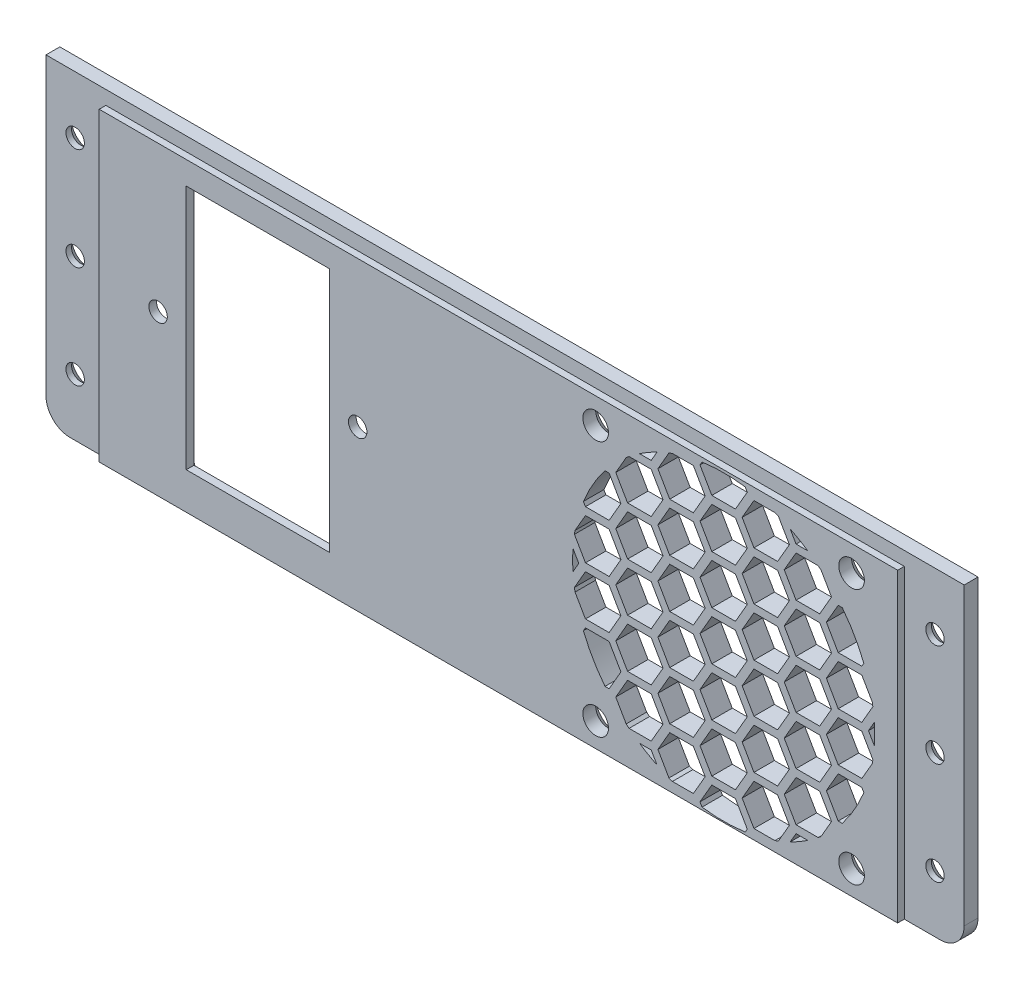
SolidWorks part; units mm, degrees
ref_plane "Front Plane" through (0, 0, 0) normal (0, 0, 1) x (1, 0, 0)
ref_plane "Top Plane" through (0, 0, 0) normal (0, 1, 0) x (1, 0, 0)
ref_plane "Right Plane" through (0, 0, 0) normal (1, 0, 0) x (0, 0, -1)
sketch "Sketch1" plane through (0, 0, 0) normal (0, 0, 1) x (1, 0, 0)
  line L1 (-90, -31.5) -> (90, -31.5)
  line L2 (-90, -31.5) -> (-90, 31.5)
  line L3 (-90, 31.5) -> (90, 31.5)
  line L4 (90, -31.5) -> (90, 31.5)
  line L5 (-90, -31.5) -> (90, 31.5) construction
  line L6 (-90, 31.5) -> (90, -31.5) construction
  point P0 (0, 0)
  dimension "D1" = 180
  dimension "D2" = 63
extrude "Boss-Extrude1" add sketch "Sketch1" along normal blind 3
fillet "Fillet1" radius 5 2 edges at (-90, -31.5, 1.5) (90, -31.5, 1.5)
sketch "Sketch2" plane through (0, 0, 3) normal (0, 0, 1) x (1, 0, 0)
  line L0 (-85, -31.5) -> (85, -31.5) construction
  line L1 (-78, -31.5) -> (78, -31.5)
  line L2 (-78, -31.5) -> (-78, 31.5)
  line L3 (-78, 31.5) -> (78, 31.5)
  line L4 (78, -31.5) -> (78, 31.5)
  line L5 (90, 31.5) -> (-90, 31.5) construction
  dimension "D1" = 12
  dimension "D2" = 12
extrude "Boss-Extrude2" add sketch "Sketch2" along normal blind 4
sketch "Sketch3" plane through (0, 0, 0) normal (0, 0, -1) x (-1, 0, 0)
  line L0 (-90, -26.5) -> (-90, 31.5) construction
  line L2 (90, -26.5) -> (90, 31.5) construction
  point P0 (-84, 20)
  point P2 (-84, -20)
  point P4 (84, 20)
  point P6 (84, -20)
  point P8 (-84, 0)
  point P10 (84, 0)
  dimension "D1" = 6
  dimension "D2" = 20
  dimension "D3" = 20
  dimension "D4" = 6
  dimension "D5" = 20
  dimension "D6" = 20
hole_wizard "CSK for M3 Flat Head Machine Screw1" positions "Sketch3" profile "Sketch4" countersink size "M3" standard "ANSI Metric"
sketch "Sketch4" plane through (84, 20, 0) normal (1, 0, 0) x (0, 1, 0)
  line L0 (0, 0) -> (0, 9.0815)
  line L1 (0, 9.0815) -> (1.8, 8)
  line L2 (1.8, 8) -> (1.8, 1.6)
  line L3 (1.8, 1.6) -> (3.4, 0)
  line L5 (3.4, 0) -> (0, 0)
  line L6 (-1.8, 1.6) -> (-3.4, 0) construction
  line L10 (0, 9.0815) -> (-1.8, 8) construction
  line L11 (0, -6.35) -> (0, 107.95) construction
  dimension "Hole Dia." = 3.6
  dimension "Hole Depth" = 8
  dimension "Near C'Sink Dia." = 6.8
  dimension "Near C'Sink Angle" = 90
  dimension "Drill Angle" = 118
sketch "Sketch5" plane through (0, 0, 0) normal (0, 0, -1) x (-1, 0, 0)
  line L0 (32, 30) -> (21, 0)
  line L1 (62, 30) -> (32, 30)
  line L2 (62, 30) -> (62, -30)
  line L3 (62, -30) -> (32, -30)
  line L4 (32, 30) -> (32, -30)
  line L5 (21, 0) -> (32, -30)
  line L6 (62, -30) -> (73, 0)
  line L7 (73, 0) -> (62, 30)
  line L8 (90, 31.5) -> (90, -26.5) construction
  point P8 (62, 0)
  dimension "D1" = 30
  dimension "D2" = 60
  dimension "D3" = 11
  dimension "D4" = 11
  dimension "D5" = 28
extrude "Cut-Extrude1" cut sketch "Sketch5" against normal blind 2.5 contours L0 L5 L4 | L1 L4 L3 L2 | L6 L7 L2 region at (-28.3333, 0, 0) region at (-47, 0, 0) region at (-65.6667, 0, 0)
sketch "Sketch6" plane through (0, 0, 2.5) normal (0, 0, -1) x (-1, 0, 0)
  line L0 (62, 30) -> (32, 30) construction
  line L1 (61, -24) -> (33, -24)
  line L2 (61, -24) -> (61, 24)
  line L3 (61, 24) -> (33, 24)
  line L4 (33, -24) -> (33, 24)
  line L5 (61, -24) -> (33, 24) construction
  line L6 (61, 24) -> (33, -24) construction
  point P0 (47, 0)
  point P7 (47, 30)
  dimension "D1" = 28
  dimension "D2" = 48
extrude "Cut-Extrude2" cut sketch "Sketch6" against normal through all
fillet "Fillet2" radius 2 6 edges at (-21, 0, 1.25) (-32, -30, 1.25) (-62, -30, 1.25) (-73, 0, 1.25) (-62, 30, 1.25) (-32, 30, 1.25)
sketch "Sketch7" plane through (0, 0, 2.5) normal (0, 0, -1) x (-1, 0, 0)
  line L0 (27.5, 0) -> (66.5, 0) construction
  line L2 (61, 24) -> (33, 24) construction
  point P0 (27.5, 0)
  point P2 (66.5, 0)
  point P15 (47, 24)
  point P16 (47, 0)
  dimension "D1" = 39
hole_wizard "M3 Clearance Hole1" positions "Sketch7" profile "Sketch8" hole size "M3" standard "ANSI Metric"
sketch "Sketch8" plane through (-27.5, 0, 2.5) normal (1, 0, 0) x (0, 1, 0)
  line L0 (0, 0) -> (0, 9.0815)
  line L1 (0, 9.0815) -> (1.8, 8)
  line L2 (1.8, 8) -> (1.8, 0)
  line L5 (1.8, 0) -> (0, 0)
  line L10 (0, 9.0815) -> (-1.8, 8) construction
  line L11 (0, -6.35) -> (0, 107.95) construction
  dimension "Hole Dia." = 3.6
  dimension "Hole Depth" = 8
  dimension "Drill Angle" = 118
sketch "Sketch9" plane through (0, 0, 7) normal (0, 0, 1) x (1, 0, 0)
  line L0 (-78, -31.5) -> (78, -31.5) construction
  line L1 (14, -31.5) -> (74, -31.5)
  line L2 (14, -31.5) -> (14, 28.5)
  line L3 (14, 28.5) -> (74, 28.5)
  line L4 (74, -31.5) -> (74, 28.5)
  line L5 (14, -31.5) -> (74, 28.5) construction
  line L6 (14, 28.5) -> (74, -31.5) construction
  line L11 (78, -31.5) -> (78, 31.5) construction
  line L13 (69, -26.5) -> (19, -26.5)
  line L14 (69, -26.5) -> (69, 23.5)
  line L15 (69, 23.5) -> (19, 23.5)
  line L16 (19, -26.5) -> (19, 23.5)
  line L17 (69, -26.5) -> (19, 23.5) construction
  line L18 (69, 23.5) -> (19, -26.5) construction
  point P0 (44, -1.5)
  point P10 (44, -1.5)
  dimension "D1" = 60
  dimension "D2" = 60
  dimension "D3" = 4
  dimension "D4" = 50
sketch "Sketch12" plane through (0, 0, 0) normal (0, 0, -1) x (-1, 0, 0)
  point P0 (-19, 23.5)
  point P2 (-19, -26.5)
  point P4 (-69, -26.5)
  point P6 (-69, 23.5)
hole_wizard "CSK for M4 Flat Head Machine Screw2" positions "Sketch12" profile "Sketch14" countersink size "M4" standard "ANSI Metric" end condition through all
sketch "Sketch14" plane through (19, 23.5, 0) normal (1, 0, 0) x (0, 1, 0)
  line L0 (0, 0) -> (0, 7)
  line L1 (0, 7) -> (2.5, 7)
  line L2 (2.5, 7) -> (2.5, 1.5)
  line L3 (2.5, 1.5) -> (4, 0)
  line L5 (4, 0) -> (0, 0)
  line L6 (-2.5, 1.5) -> (-4, 0) construction
  line L11 (0, -6.35) -> (0, 107.95) construction
  dimension "Thru Hole Dia." = 5
  dimension "Thru Hole Depth" = 7
  dimension "Near C'Sink Dia." = 8
  dimension "Near C'Sink Angle" = 90
sketch "Sketch15" plane through (0, 0, 7) normal (0, 0, 1) x (1, 0, 0)
  line L0 (-78, -31.5) -> (78, -31.5) construction
  line L1 (74, -31.5) -> (-21, -31.5)
  line L2 (74, -31.5) -> (74, 31.5)
  line L3 (74, 31.5) -> (-21, 31.5)
  line L4 (-21, -31.5) -> (-21, 31.5)
  line L5 (78, 31.5) -> (-78, 31.5) construction
  line L6 (78, -31.5) -> (78, 31.5) construction
  dimension "D1" = 4
  dimension "D2" = 95
extrude "Cut-Extrude3" cut sketch "Sketch15" against normal blind 3
sketch "Sketch16" plane through (0, 0, 0) normal (0, 0, -1) x (-1, 0, 0)
  circle A4 centre (-64, 13.5) radius 4
  circle A53 centre (-69, 23.5) radius 4 construction
  circle A54 centre (-69, 23.5) radius 4
  circle A55 centre (-19, 23.5) radius 4 construction
  circle A56 centre (-19, 23.5) radius 4
  circle A57 centre (-59, 23.5) radius 4
  circle A58 centre (-49, 23.5) radius 4
  circle A59 centre (-39, 23.5) radius 4
  circle A60 centre (-29, 23.5) radius 4
  circle A61 centre (-54, 13.5) radius 4
  circle A62 centre (-44, 13.5) radius 4
  circle A63 centre (-34, 13.5) radius 4
  circle A64 centre (-24, 13.5) radius 4
  circle A65 centre (-14, 13.5) radius 4
  circle A66 centre (-4, 13.5) radius 4
  circle A67 centre (6, 13.5) radius 4
  circle A68 centre (-54, -6.5) radius 4
  circle A69 centre (-44, -6.5) radius 4
  circle A70 centre (-34, -6.5) radius 4
  circle A71 centre (-24, -6.5) radius 4
  circle A72 centre (-14, -6.5) radius 4
  circle A73 centre (-4, -6.5) radius 4
  circle A74 centre (6, -6.5) radius 4
  circle A75 centre (-64, -6.5) radius 4
  circle A76 centre (-59, 23.5) radius 4
  circle A77 centre (-49, 23.5) radius 4
  circle A78 centre (-39, 23.5) radius 4
  circle A79 centre (-29, 23.5) radius 4
  circle A80 centre (-19, 23.5) radius 4
  circle A81 centre (-9, 23.5) radius 4
  circle A82 centre (1, 23.5) radius 4
  circle A83 centre (-59, 3.5) radius 4
  circle A84 centre (-49, 3.5) radius 4
  circle A85 centre (-39, 3.5) radius 4
  circle A86 centre (-29, 3.5) radius 4
  circle A87 centre (-19, 3.5) radius 4
  circle A88 centre (-9, 3.5) radius 4
  circle A89 centre (1, 3.5) radius 4
  circle A90 centre (-59, -16.5) radius 4
  circle A91 centre (-49, -16.5) radius 4
  circle A92 centre (-39, -16.5) radius 4
  circle A93 centre (-29, -16.5) radius 4
  circle A94 centre (-19, -16.5) radius 4
  circle A95 centre (-9, -16.5) radius 4
  circle A96 centre (1, -16.5) radius 4
  circle A97 centre (-69, 3.5) radius 4
  circle A98 centre (-69, -16.5) radius 4
  dimension "D1" = 5
  dimension "D2" = 10
  dimension "D3" = 5
sketch "Sketch17" plane through (0, 0, 0) normal (0, 0, -1) x (-1, 0, 0)
  circle A0 centre (-44, -1.5) radius 29.5
  dimension "D1" = 59
extrude "Cut-Extrude7" cut sketch "Sketch17" against normal through all
sketch "Sketch18" plane through (0, 31.5, 0) normal (0, 1, 0) x (1, 0, 0)
  line L1 (-90, -3) -> (90, -3)
  line L2 (-90, -3) -> (-90, -11)
  line L3 (-90, -11) -> (90, -11)
  line L4 (90, -3) -> (90, -11)
  dimension "D1" = 8
extrude "Cut-Extrude8" cut sketch "Sketch18" against normal blind 3
sketch "Sketch20" plane through (0, 0, 0) normal (0, 0, -1) x (-1, 0, 0)
  line L0 (-90, -26.5) -> (-90, 31.5) construction
  line L1 (-10, 28) -> (20, 28)
  line L2 (-10, 28) -> (-10, -31)
  line L3 (-10, -31) -> (20, -31)
  line L4 (20, 28) -> (20, -31)
  line L5 (-10, 28) -> (20, -31) construction
  line L6 (-10, -31) -> (20, 28) construction
  circle A0 centre (-44, -1.5) radius 29.5 construction
  point P0 (5, -1.5)
  dimension "D1" = 30
  dimension "D2" = 95
extrude "Cut-Extrude9" cut sketch "Sketch20" against normal through all
sketch "Sketch19" plane through (0, 0, 0) normal (0, 0, -1) x (-1, 0, 0)
  line L0 (-44, -1.5) -> (-35.7728, 3.25) construction
  line L1 (-39.3812, -1.5) -> (-41.6906, 2.5)
  line L2 (-41.6906, 2.5) -> (-46.3094, 2.5)
  line L3 (-46.3094, 2.5) -> (-48.6188, -1.5)
  line L4 (-48.6188, -1.5) -> (-46.3094, -5.5)
  line L5 (-46.3094, -5.5) -> (-41.6906, -5.5)
  line L6 (-41.6906, -5.5) -> (-39.3812, -1.5)
  line L7 (-31.154, 3.25) -> (-33.4634, 7.25)
  line L8 (-33.4634, 7.25) -> (-38.0822, 7.25)
  line L9 (-38.0822, 7.25) -> (-40.3916, 3.25)
  line L10 (-40.3916, 3.25) -> (-38.0822, -0.75)
  line L11 (-38.0822, -0.75) -> (-33.4634, -0.75)
  line L12 (-33.4634, -0.75) -> (-31.154, 3.25)
  line L13 (-44, -1.5) -> (-35.7728, -1.5) construction
  line L14 (-39.3812, -11) -> (-41.6906, -7)
  line L15 (-41.6906, -7) -> (-46.3094, -7)
  line L16 (-46.3094, -7) -> (-48.6188, -11)
  line L17 (-48.6188, -11) -> (-46.3094, -15)
  line L18 (-46.3094, -15) -> (-41.6906, -15)
  line L19 (-41.6906, -15) -> (-39.3812, -11)
  line L20 (-31.154, -6.25) -> (-33.4634, -2.25)
  line L21 (-33.4634, -2.25) -> (-38.0822, -2.25)
  line L22 (-38.0822, -2.25) -> (-40.3916, -6.25)
  line L23 (-40.3916, -6.25) -> (-38.0822, -10.25)
  line L24 (-38.0822, -10.25) -> (-33.4634, -10.25)
  line L25 (-33.4634, -10.25) -> (-31.154, -6.25)
  line L26 (-22.9212, -1.5) -> (-25.2306, 2.5)
  line L27 (-25.2306, 2.5) -> (-29.8494, 2.5)
  line L28 (-29.8494, 2.5) -> (-32.1588, -1.5)
  line L29 (-32.1588, -1.5) -> (-29.8494, -5.5)
  line L30 (-29.8494, -5.5) -> (-25.2306, -5.5)
  line L31 (-25.2306, -5.5) -> (-22.9212, -1.5)
  line L32 (-6.4612, -1.5) -> (-8.7706, 2.5)
  line L33 (-8.7706, 2.5) -> (-13.3894, 2.5)
  line L34 (-13.3894, 2.5) -> (-15.6988, -1.5)
  line L35 (-15.6988, -1.5) -> (-13.3894, -5.5)
  line L36 (-13.3894, -5.5) -> (-8.7706, -5.5)
  line L37 (-8.7706, -5.5) -> (-6.4612, -1.5)
  line L38 (-22.9212, -11) -> (-25.2306, -7)
  line L39 (-25.2306, -7) -> (-29.8494, -7)
  line L40 (-29.8494, -7) -> (-32.1588, -11)
  line L41 (-32.1588, -11) -> (-29.8494, -15)
  line L42 (-29.8494, -15) -> (-25.2306, -15)
  line L43 (-25.2306, -15) -> (-22.9212, -11)
  line L44 (-6.4612, -11) -> (-8.7706, -7)
  line L45 (-8.7706, -7) -> (-13.3894, -7)
  line L46 (-13.3894, -7) -> (-15.6988, -11)
  line L47 (-15.6988, -11) -> (-13.3894, -15)
  line L48 (-13.3894, -15) -> (-8.7706, -15)
  line L49 (-8.7706, -15) -> (-6.4612, -11)
  line L50 (-22.9212, -20.5) -> (-25.2306, -16.5)
  line L51 (-25.2306, -16.5) -> (-29.8494, -16.5)
  line L52 (-29.8494, -16.5) -> (-32.1588, -20.5)
  line L53 (-32.1588, -20.5) -> (-29.8494, -24.5)
  line L54 (-29.8494, -24.5) -> (-25.2306, -24.5)
  line L55 (-25.2306, -24.5) -> (-22.9212, -20.5)
  line L56 (-6.4612, -20.5) -> (-8.7706, -16.5)
  line L57 (-8.7706, -16.5) -> (-13.3894, -16.5)
  line L58 (-13.3894, -16.5) -> (-15.6988, -20.5)
  line L59 (-15.6988, -20.5) -> (-13.3894, -24.5)
  line L60 (-13.3894, -24.5) -> (-8.7706, -24.5)
  line L61 (-8.7706, -24.5) -> (-6.4612, -20.5)
  line L62 (-22.9212, -30) -> (-25.2306, -26)
  line L63 (-25.2306, -26) -> (-29.8494, -26)
  line L64 (-29.8494, -26) -> (-32.1588, -30)
  line L65 (-32.1588, -30) -> (-29.8494, -34)
  line L66 (-29.8494, -34) -> (-25.2306, -34)
  line L67 (-25.2306, -34) -> (-22.9212, -30)
  line L68 (-6.4612, -30) -> (-8.7706, -26)
  line L69 (-8.7706, -26) -> (-13.3894, -26)
  line L70 (-13.3894, -26) -> (-15.6988, -30)
  line L71 (-15.6988, -30) -> (-13.3894, -34)
  line L72 (-13.3894, -34) -> (-8.7706, -34)
  line L73 (-8.7706, -34) -> (-6.4612, -30)
  line L74 (-39.3812, -11) -> (-41.6906, -7)
  line L75 (-41.6906, -7) -> (-46.3094, -7)
  line L76 (-46.3094, -7) -> (-48.6188, -11)
  line L77 (-48.6188, -11) -> (-46.3094, -15)
  line L78 (-46.3094, -15) -> (-41.6906, -15)
  line L79 (-41.6906, -15) -> (-39.3812, -11)
  line L80 (-39.3812, -20.5) -> (-41.6906, -16.5)
  line L81 (-41.6906, -16.5) -> (-46.3094, -16.5)
  line L82 (-46.3094, -16.5) -> (-48.6188, -20.5)
  line L83 (-48.6188, -20.5) -> (-46.3094, -24.5)
  line L84 (-46.3094, -24.5) -> (-41.6906, -24.5)
  line L85 (-41.6906, -24.5) -> (-39.3812, -20.5)
  line L86 (-39.3812, -30) -> (-41.6906, -26)
  line L87 (-41.6906, -26) -> (-46.3094, -26)
  line L88 (-46.3094, -26) -> (-48.6188, -30)
  line L89 (-48.6188, -30) -> (-46.3094, -34)
  line L90 (-46.3094, -34) -> (-41.6906, -34)
  line L91 (-41.6906, -34) -> (-39.3812, -30)
  line L92 (-39.3812, 8) -> (-41.6906, 12)
  line L93 (-41.6906, 12) -> (-46.3094, 12)
  line L94 (-46.3094, 12) -> (-48.6188, 8)
  line L95 (-48.6188, 8) -> (-46.3094, 4)
  line L96 (-46.3094, 4) -> (-41.6906, 4)
  line L97 (-41.6906, 4) -> (-39.3812, 8)
  line L98 (-22.9212, 8) -> (-25.2306, 12)
  line L99 (-25.2306, 12) -> (-29.8494, 12)
  line L100 (-29.8494, 12) -> (-32.1588, 8)
  line L101 (-32.1588, 8) -> (-29.8494, 4)
  line L102 (-29.8494, 4) -> (-25.2306, 4)
  line L103 (-25.2306, 4) -> (-22.9212, 8)
  line L104 (-6.4612, 8) -> (-8.7706, 12)
  line L105 (-8.7706, 12) -> (-13.3894, 12)
  line L106 (-13.3894, 12) -> (-15.6988, 8)
  line L107 (-15.6988, 8) -> (-13.3894, 4)
  line L108 (-13.3894, 4) -> (-8.7706, 4)
  line L109 (-8.7706, 4) -> (-6.4612, 8)
  line L110 (-39.3812, 17.5) -> (-41.6906, 21.5)
  line L111 (-41.6906, 21.5) -> (-46.3094, 21.5)
  line L112 (-46.3094, 21.5) -> (-48.6188, 17.5)
  line L113 (-48.6188, 17.5) -> (-46.3094, 13.5)
  line L114 (-46.3094, 13.5) -> (-41.6906, 13.5)
  line L115 (-41.6906, 13.5) -> (-39.3812, 17.5)
  line L116 (-22.9212, 17.5) -> (-25.2306, 21.5)
  line L117 (-25.2306, 21.5) -> (-29.8494, 21.5)
  line L118 (-29.8494, 21.5) -> (-32.1588, 17.5)
  line L119 (-32.1588, 17.5) -> (-29.8494, 13.5)
  line L120 (-29.8494, 13.5) -> (-25.2306, 13.5)
  line L121 (-25.2306, 13.5) -> (-22.9212, 17.5)
  line L122 (-6.4612, 17.5) -> (-8.7706, 21.5)
  line L123 (-8.7706, 21.5) -> (-13.3894, 21.5)
  line L124 (-13.3894, 21.5) -> (-15.6988, 17.5)
  line L125 (-15.6988, 17.5) -> (-13.3894, 13.5)
  line L126 (-13.3894, 13.5) -> (-8.7706, 13.5)
  line L127 (-8.7706, 13.5) -> (-6.4612, 17.5)
  line L128 (-39.3812, 27) -> (-41.6906, 31)
  line L129 (-41.6906, 31) -> (-46.3094, 31)
  line L130 (-46.3094, 31) -> (-48.6188, 27)
  line L131 (-48.6188, 27) -> (-46.3094, 23)
  line L132 (-46.3094, 23) -> (-41.6906, 23)
  line L133 (-41.6906, 23) -> (-39.3812, 27)
  line L134 (-22.9212, 27) -> (-25.2306, 31)
  line L135 (-25.2306, 31) -> (-29.8494, 31)
  line L136 (-29.8494, 31) -> (-32.1588, 27)
  line L137 (-32.1588, 27) -> (-29.8494, 23)
  line L138 (-29.8494, 23) -> (-25.2306, 23)
  line L139 (-25.2306, 23) -> (-22.9212, 27)
  line L140 (-6.4612, 27) -> (-8.7706, 31)
  line L141 (-8.7706, 31) -> (-13.3894, 31)
  line L142 (-13.3894, 31) -> (-15.6988, 27)
  line L143 (-15.6988, 27) -> (-13.3894, 23)
  line L144 (-13.3894, 23) -> (-8.7706, 23)
  line L145 (-8.7706, 23) -> (-6.4612, 27)
  line L146 (-31.154, 12.75) -> (-33.4634, 16.75)
  line L147 (-33.4634, 16.75) -> (-38.0822, 16.75)
  line L148 (-38.0822, 16.75) -> (-40.3916, 12.75)
  line L149 (-40.3916, 12.75) -> (-38.0822, 8.75)
  line L150 (-38.0822, 8.75) -> (-33.4634, 8.75)
  line L151 (-33.4634, 8.75) -> (-31.154, 12.75)
  line L152 (-31.154, 22.25) -> (-33.4634, 26.25)
  line L153 (-33.4634, 26.25) -> (-38.0822, 26.25)
  line L154 (-38.0822, 26.25) -> (-40.3916, 22.25)
  line L155 (-40.3916, 22.25) -> (-38.0822, 18.25)
  line L156 (-38.0822, 18.25) -> (-33.4634, 18.25)
  line L157 (-33.4634, 18.25) -> (-31.154, 22.25)
  line L158 (-31.154, -15.75) -> (-33.4634, -11.75)
  line L159 (-33.4634, -11.75) -> (-38.0822, -11.75)
  line L160 (-38.0822, -11.75) -> (-40.3916, -15.75)
  line L161 (-40.3916, -15.75) -> (-38.0822, -19.75)
  line L162 (-38.0822, -19.75) -> (-33.4634, -19.75)
  line L163 (-33.4634, -19.75) -> (-31.154, -15.75)
  line L164 (-31.154, -25.25) -> (-33.4634, -21.25)
  line L165 (-33.4634, -21.25) -> (-38.0822, -21.25)
  line L166 (-38.0822, -21.25) -> (-40.3916, -25.25)
  line L167 (-40.3916, -25.25) -> (-38.0822, -29.25)
  line L168 (-38.0822, -29.25) -> (-33.4634, -29.25)
  line L169 (-33.4634, -29.25) -> (-31.154, -25.25)
  line L170 (-31.154, -34.75) -> (-33.4634, -30.75)
  line L171 (-33.4634, -30.75) -> (-38.0822, -30.75)
  line L172 (-38.0822, -30.75) -> (-40.3916, -34.75)
  line L173 (-40.3916, -34.75) -> (-38.0822, -38.75)
  line L174 (-38.0822, -38.75) -> (-33.4634, -38.75)
  line L175 (-33.4634, -38.75) -> (-31.154, -34.75)
  line L176 (-14.694, 22.25) -> (-17.0034, 26.25)
  line L177 (-17.0034, 26.25) -> (-21.6222, 26.25)
  line L178 (-21.6222, 26.25) -> (-23.9316, 22.25)
  line L179 (-23.9316, 22.25) -> (-21.6222, 18.25)
  line L180 (-21.6222, 18.25) -> (-17.0034, 18.25)
  line L181 (-17.0034, 18.25) -> (-14.694, 22.25)
  line L182 (-14.694, 12.75) -> (-17.0034, 16.75)
  line L183 (-17.0034, 16.75) -> (-21.6222, 16.75)
  line L184 (-21.6222, 16.75) -> (-23.9316, 12.75)
  line L185 (-23.9316, 12.75) -> (-21.6222, 8.75)
  line L186 (-21.6222, 8.75) -> (-17.0034, 8.75)
  line L187 (-17.0034, 8.75) -> (-14.694, 12.75)
  line L188 (-14.694, 3.25) -> (-17.0034, 7.25)
  line L189 (-17.0034, 7.25) -> (-21.6222, 7.25)
  line L190 (-21.6222, 7.25) -> (-23.9316, 3.25)
  line L191 (-23.9316, 3.25) -> (-21.6222, -0.75)
  line L192 (-21.6222, -0.75) -> (-17.0034, -0.75)
  line L193 (-17.0034, -0.75) -> (-14.694, 3.25)
  line L194 (-14.694, -6.25) -> (-17.0034, -2.25)
  line L195 (-17.0034, -2.25) -> (-21.6222, -2.25)
  line L196 (-21.6222, -2.25) -> (-23.9316, -6.25)
  line L197 (-23.9316, -6.25) -> (-21.6222, -10.25)
  line L198 (-21.6222, -10.25) -> (-17.0034, -10.25)
  line L199 (-17.0034, -10.25) -> (-14.694, -6.25)
  line L200 (-14.694, -15.75) -> (-17.0034, -11.75)
  line L201 (-17.0034, -11.75) -> (-21.6222, -11.75)
  line L202 (-21.6222, -11.75) -> (-23.9316, -15.75)
  line L203 (-23.9316, -15.75) -> (-21.6222, -19.75)
  line L204 (-21.6222, -19.75) -> (-17.0034, -19.75)
  line L205 (-17.0034, -19.75) -> (-14.694, -15.75)
  line L206 (-14.694, -25.25) -> (-17.0034, -21.25)
  line L207 (-17.0034, -21.25) -> (-21.6222, -21.25)
  line L208 (-21.6222, -21.25) -> (-23.9316, -25.25)
  line L209 (-23.9316, -25.25) -> (-21.6222, -29.25)
  line L210 (-21.6222, -29.25) -> (-17.0034, -29.25)
  line L211 (-17.0034, -29.25) -> (-14.694, -25.25)
  line L212 (-55.8412, 27) -> (-58.1506, 31)
  line L213 (-58.1506, 31) -> (-62.7694, 31)
  line L214 (-62.7694, 31) -> (-65.0788, 27)
  line L215 (-65.0788, 27) -> (-62.7694, 23)
  line L216 (-62.7694, 23) -> (-58.1506, 23)
  line L217 (-58.1506, 23) -> (-55.8412, 27)
  line L218 (-55.8412, 17.5) -> (-58.1506, 21.5)
  line L219 (-58.1506, 21.5) -> (-62.7694, 21.5)
  line L220 (-62.7694, 21.5) -> (-65.0788, 17.5)
  line L221 (-65.0788, 17.5) -> (-62.7694, 13.5)
  line L222 (-62.7694, 13.5) -> (-58.1506, 13.5)
  line L223 (-58.1506, 13.5) -> (-55.8412, 17.5)
  line L224 (-47.614, 22.25) -> (-49.9234, 26.25)
  line L225 (-49.9234, 26.25) -> (-54.5422, 26.25)
  line L226 (-54.5422, 26.25) -> (-56.8516, 22.25)
  line L227 (-56.8516, 22.25) -> (-54.5422, 18.25)
  line L228 (-54.5422, 18.25) -> (-49.9234, 18.25)
  line L229 (-49.9234, 18.25) -> (-47.614, 22.25)
  line L230 (-47.614, 12.75) -> (-49.9234, 16.75)
  line L231 (-49.9234, 16.75) -> (-54.5422, 16.75)
  line L232 (-54.5422, 16.75) -> (-56.8516, 12.75)
  line L233 (-56.8516, 12.75) -> (-54.5422, 8.75)
  line L234 (-54.5422, 8.75) -> (-49.9234, 8.75)
  line L235 (-49.9234, 8.75) -> (-47.614, 12.75)
  line L236 (-55.8412, 8) -> (-58.1506, 12)
  line L237 (-58.1506, 12) -> (-62.7694, 12)
  line L238 (-62.7694, 12) -> (-65.0788, 8)
  line L239 (-65.0788, 8) -> (-62.7694, 4)
  line L240 (-62.7694, 4) -> (-58.1506, 4)
  line L241 (-58.1506, 4) -> (-55.8412, 8)
  line L242 (-47.614, 3.25) -> (-49.9234, 7.25)
  line L243 (-49.9234, 7.25) -> (-54.5422, 7.25)
  line L244 (-54.5422, 7.25) -> (-56.8516, 3.25)
  line L245 (-56.8516, 3.25) -> (-54.5422, -0.75)
  line L246 (-54.5422, -0.75) -> (-49.9234, -0.75)
  line L247 (-49.9234, -0.75) -> (-47.614, 3.25)
  line L248 (-55.8412, -1.5) -> (-58.1506, 2.5)
  line L249 (-58.1506, 2.5) -> (-62.7694, 2.5)
  line L250 (-62.7694, 2.5) -> (-65.0788, -1.5)
  line L251 (-65.0788, -1.5) -> (-62.7694, -5.5)
  line L252 (-62.7694, -5.5) -> (-58.1506, -5.5)
  line L253 (-58.1506, -5.5) -> (-55.8412, -1.5)
  line L254 (-47.614, -6.25) -> (-49.9234, -2.25)
  line L255 (-49.9234, -2.25) -> (-54.5422, -2.25)
  line L256 (-54.5422, -2.25) -> (-56.8516, -6.25)
  line L257 (-56.8516, -6.25) -> (-54.5422, -10.25)
  line L258 (-54.5422, -10.25) -> (-49.9234, -10.25)
  line L259 (-49.9234, -10.25) -> (-47.614, -6.25)
  line L260 (-55.8412, -11) -> (-58.1506, -7)
  line L261 (-58.1506, -7) -> (-62.7694, -7)
  line L262 (-62.7694, -7) -> (-65.0788, -11)
  line L263 (-65.0788, -11) -> (-62.7694, -15)
  line L264 (-62.7694, -15) -> (-58.1506, -15)
  line L265 (-58.1506, -15) -> (-55.8412, -11)
  line L266 (-47.614, -15.75) -> (-49.9234, -11.75)
  line L267 (-49.9234, -11.75) -> (-54.5422, -11.75)
  line L268 (-54.5422, -11.75) -> (-56.8516, -15.75)
  line L269 (-56.8516, -15.75) -> (-54.5422, -19.75)
  line L270 (-54.5422, -19.75) -> (-49.9234, -19.75)
  line L271 (-49.9234, -19.75) -> (-47.614, -15.75)
  line L272 (-55.8412, -20.5) -> (-58.1506, -16.5)
  line L273 (-58.1506, -16.5) -> (-62.7694, -16.5)
  line L274 (-62.7694, -16.5) -> (-65.0788, -20.5)
  line L275 (-65.0788, -20.5) -> (-62.7694, -24.5)
  line L276 (-62.7694, -24.5) -> (-58.1506, -24.5)
  line L277 (-58.1506, -24.5) -> (-55.8412, -20.5)
  line L278 (-47.614, -25.25) -> (-49.9234, -21.25)
  line L279 (-49.9234, -21.25) -> (-54.5422, -21.25)
  line L280 (-54.5422, -21.25) -> (-56.8516, -25.25)
  line L281 (-56.8516, -25.25) -> (-54.5422, -29.25)
  line L282 (-54.5422, -29.25) -> (-49.9234, -29.25)
  line L283 (-49.9234, -29.25) -> (-47.614, -25.25)
  line L284 (-55.8412, -30) -> (-58.1506, -26)
  line L285 (-58.1506, -26) -> (-62.7694, -26)
  line L286 (-62.7694, -26) -> (-65.0788, -30)
  line L287 (-65.0788, -30) -> (-62.7694, -34)
  line L288 (-62.7694, -34) -> (-58.1506, -34)
  line L289 (-58.1506, -34) -> (-55.8412, -30)
  line L290 (-47.614, -34.75) -> (-49.9234, -30.75)
  line L291 (-49.9234, -30.75) -> (-54.5422, -30.75)
  line L292 (-54.5422, -30.75) -> (-56.8516, -34.75)
  line L293 (-56.8516, -34.75) -> (-54.5422, -38.75)
  line L294 (-54.5422, -38.75) -> (-49.9234, -38.75)
  line L295 (-49.9234, -38.75) -> (-47.614, -34.75)
  line L296 (-72.3012, 27) -> (-74.6106, 31)
  line L297 (-74.6106, 31) -> (-79.2294, 31)
  line L298 (-79.2294, 31) -> (-81.5388, 27)
  line L299 (-81.5388, 27) -> (-79.2294, 23)
  line L300 (-79.2294, 23) -> (-74.6106, 23)
  line L301 (-74.6106, 23) -> (-72.3012, 27)
  line L302 (-72.3012, 17.5) -> (-74.6106, 21.5)
  line L303 (-74.6106, 21.5) -> (-79.2294, 21.5)
  line L304 (-79.2294, 21.5) -> (-81.5388, 17.5)
  line L305 (-81.5388, 17.5) -> (-79.2294, 13.5)
  line L306 (-79.2294, 13.5) -> (-74.6106, 13.5)
  line L307 (-74.6106, 13.5) -> (-72.3012, 17.5)
  line L308 (-64.074, 22.25) -> (-66.3834, 26.25)
  line L309 (-66.3834, 26.25) -> (-71.0022, 26.25)
  line L310 (-71.0022, 26.25) -> (-73.3116, 22.25)
  line L311 (-73.3116, 22.25) -> (-71.0022, 18.25)
  line L312 (-71.0022, 18.25) -> (-66.3834, 18.25)
  line L313 (-66.3834, 18.25) -> (-64.074, 22.25)
  line L314 (-64.074, 12.75) -> (-66.3834, 16.75)
  line L315 (-66.3834, 16.75) -> (-71.0022, 16.75)
  line L316 (-71.0022, 16.75) -> (-73.3116, 12.75)
  line L317 (-73.3116, 12.75) -> (-71.0022, 8.75)
  line L318 (-71.0022, 8.75) -> (-66.3834, 8.75)
  line L319 (-66.3834, 8.75) -> (-64.074, 12.75)
  line L320 (-72.3012, 8) -> (-74.6106, 12)
  line L321 (-74.6106, 12) -> (-79.2294, 12)
  line L322 (-79.2294, 12) -> (-81.5388, 8)
  line L323 (-81.5388, 8) -> (-79.2294, 4)
  line L324 (-79.2294, 4) -> (-74.6106, 4)
  line L325 (-74.6106, 4) -> (-72.3012, 8)
  line L326 (-64.074, 3.25) -> (-66.3834, 7.25)
  line L327 (-66.3834, 7.25) -> (-71.0022, 7.25)
  line L328 (-71.0022, 7.25) -> (-73.3116, 3.25)
  line L329 (-73.3116, 3.25) -> (-71.0022, -0.75)
  line L330 (-71.0022, -0.75) -> (-66.3834, -0.75)
  line L331 (-66.3834, -0.75) -> (-64.074, 3.25)
  line L332 (-72.3012, -1.5) -> (-74.6106, 2.5)
  line L333 (-74.6106, 2.5) -> (-79.2294, 2.5)
  line L334 (-79.2294, 2.5) -> (-81.5388, -1.5)
  line L335 (-81.5388, -1.5) -> (-79.2294, -5.5)
  line L336 (-79.2294, -5.5) -> (-74.6106, -5.5)
  line L337 (-74.6106, -5.5) -> (-72.3012, -1.5)
  line L338 (-64.074, -6.25) -> (-66.3834, -2.25)
  line L339 (-66.3834, -2.25) -> (-71.0022, -2.25)
  line L340 (-71.0022, -2.25) -> (-73.3116, -6.25)
  line L341 (-73.3116, -6.25) -> (-71.0022, -10.25)
  line L342 (-71.0022, -10.25) -> (-66.3834, -10.25)
  line L343 (-66.3834, -10.25) -> (-64.074, -6.25)
  line L344 (-72.3012, -11) -> (-74.6106, -7)
  line L345 (-74.6106, -7) -> (-79.2294, -7)
  line L346 (-79.2294, -7) -> (-81.5388, -11)
  line L347 (-81.5388, -11) -> (-79.2294, -15)
  line L348 (-79.2294, -15) -> (-74.6106, -15)
  line L349 (-74.6106, -15) -> (-72.3012, -11)
  line L350 (-64.074, -15.75) -> (-66.3834, -11.75)
  line L351 (-66.3834, -11.75) -> (-71.0022, -11.75)
  line L352 (-71.0022, -11.75) -> (-73.3116, -15.75)
  line L353 (-73.3116, -15.75) -> (-71.0022, -19.75)
  line L354 (-71.0022, -19.75) -> (-66.3834, -19.75)
  line L355 (-66.3834, -19.75) -> (-64.074, -15.75)
  line L356 (-72.3012, -20.5) -> (-74.6106, -16.5)
  line L357 (-74.6106, -16.5) -> (-79.2294, -16.5)
  line L358 (-79.2294, -16.5) -> (-81.5388, -20.5)
  line L359 (-81.5388, -20.5) -> (-79.2294, -24.5)
  line L360 (-79.2294, -24.5) -> (-74.6106, -24.5)
  line L361 (-74.6106, -24.5) -> (-72.3012, -20.5)
  line L362 (-64.074, -25.25) -> (-66.3834, -21.25)
  line L363 (-66.3834, -21.25) -> (-71.0022, -21.25)
  line L364 (-71.0022, -21.25) -> (-73.3116, -25.25)
  line L365 (-73.3116, -25.25) -> (-71.0022, -29.25)
  line L366 (-71.0022, -29.25) -> (-66.3834, -29.25)
  line L367 (-66.3834, -29.25) -> (-64.074, -25.25)
  line L368 (-72.3012, -30) -> (-74.6106, -26)
  line L369 (-74.6106, -26) -> (-79.2294, -26)
  line L370 (-79.2294, -26) -> (-81.5388, -30)
  line L371 (-81.5388, -30) -> (-79.2294, -34)
  line L372 (-79.2294, -34) -> (-74.6106, -34)
  line L373 (-74.6106, -34) -> (-72.3012, -30)
  line L374 (-64.074, -34.75) -> (-66.3834, -30.75)
  line L375 (-66.3834, -30.75) -> (-71.0022, -30.75)
  line L376 (-71.0022, -30.75) -> (-73.3116, -34.75)
  line L377 (-73.3116, -34.75) -> (-71.0022, -38.75)
  line L378 (-71.0022, -38.75) -> (-66.3834, -38.75)
  line L379 (-66.3834, -38.75) -> (-64.074, -34.75)
  line L380 (1.766, 22.25) -> (-0.5434, 26.25)
  line L381 (-0.5434, 26.25) -> (-5.1622, 26.25)
  line L382 (-5.1622, 26.25) -> (-7.4716, 22.25)
  line L383 (-7.4716, 22.25) -> (-5.1622, 18.25)
  line L384 (-5.1622, 18.25) -> (-0.5434, 18.25)
  line L385 (-0.5434, 18.25) -> (1.766, 22.25)
  line L386 (9.9988, 27) -> (7.6894, 31)
  line L387 (7.6894, 31) -> (3.0706, 31)
  line L388 (3.0706, 31) -> (0.7612, 27)
  line L389 (0.7612, 27) -> (3.0706, 23)
  line L390 (3.0706, 23) -> (7.6894, 23)
  line L391 (7.6894, 23) -> (9.9988, 27)
  line L392 (9.9988, 17.5) -> (7.6894, 21.5)
  line L393 (7.6894, 21.5) -> (3.0706, 21.5)
  line L394 (3.0706, 21.5) -> (0.7612, 17.5)
  line L395 (0.7612, 17.5) -> (3.0706, 13.5)
  line L396 (3.0706, 13.5) -> (7.6894, 13.5)
  line L397 (7.6894, 13.5) -> (9.9988, 17.5)
  line L398 (1.766, 12.75) -> (-0.5434, 16.75)
  line L399 (-0.5434, 16.75) -> (-5.1622, 16.75)
  line L400 (-5.1622, 16.75) -> (-7.4716, 12.75)
  line L401 (-7.4716, 12.75) -> (-5.1622, 8.75)
  line L402 (-5.1622, 8.75) -> (-0.5434, 8.75)
  line L403 (-0.5434, 8.75) -> (1.766, 12.75)
  line L404 (9.9988, 8) -> (7.6894, 12)
  line L405 (7.6894, 12) -> (3.0706, 12)
  line L406 (3.0706, 12) -> (0.7612, 8)
  line L407 (0.7612, 8) -> (3.0706, 4)
  line L408 (3.0706, 4) -> (7.6894, 4)
  line L409 (7.6894, 4) -> (9.9988, 8)
  line L410 (1.766, 3.25) -> (-0.5434, 7.25)
  line L411 (-0.5434, 7.25) -> (-5.1622, 7.25)
  line L412 (-5.1622, 7.25) -> (-7.4716, 3.25)
  line L413 (-7.4716, 3.25) -> (-5.1622, -0.75)
  line L414 (-5.1622, -0.75) -> (-0.5434, -0.75)
  line L415 (-0.5434, -0.75) -> (1.766, 3.25)
  line L416 (9.9988, -1.5) -> (7.6894, 2.5)
  line L417 (7.6894, 2.5) -> (3.0706, 2.5)
  line L418 (3.0706, 2.5) -> (0.7612, -1.5)
  line L419 (0.7612, -1.5) -> (3.0706, -5.5)
  line L420 (3.0706, -5.5) -> (7.6894, -5.5)
  line L421 (7.6894, -5.5) -> (9.9988, -1.5)
  line L422 (1.766, -6.25) -> (-0.5434, -2.25)
  line L423 (-0.5434, -2.25) -> (-5.1622, -2.25)
  line L424 (-5.1622, -2.25) -> (-7.4716, -6.25)
  line L425 (-7.4716, -6.25) -> (-5.1622, -10.25)
  line L426 (-5.1622, -10.25) -> (-0.5434, -10.25)
  line L427 (-0.5434, -10.25) -> (1.766, -6.25)
  line L428 (9.9988, -11) -> (7.6894, -7)
  line L429 (7.6894, -7) -> (3.0706, -7)
  line L430 (3.0706, -7) -> (0.7612, -11)
  line L431 (0.7612, -11) -> (3.0706, -15)
  line L432 (3.0706, -15) -> (7.6894, -15)
  line L433 (7.6894, -15) -> (9.9988, -11)
  line L434 (1.766, -15.75) -> (-0.5434, -11.75)
  line L435 (-0.5434, -11.75) -> (-5.1622, -11.75)
  line L436 (-5.1622, -11.75) -> (-7.4716, -15.75)
  line L437 (-7.4716, -15.75) -> (-5.1622, -19.75)
  line L438 (-5.1622, -19.75) -> (-0.5434, -19.75)
  line L439 (-0.5434, -19.75) -> (1.766, -15.75)
  line L440 (9.9988, -20.5) -> (7.6894, -16.5)
  line L441 (7.6894, -16.5) -> (3.0706, -16.5)
  line L442 (3.0706, -16.5) -> (0.7612, -20.5)
  line L443 (0.7612, -20.5) -> (3.0706, -24.5)
  line L444 (3.0706, -24.5) -> (7.6894, -24.5)
  line L445 (7.6894, -24.5) -> (9.9988, -20.5)
  line L446 (1.766, -25.25) -> (-0.5434, -21.25)
  line L447 (-0.5434, -21.25) -> (-5.1622, -21.25)
  line L448 (-5.1622, -21.25) -> (-7.4716, -25.25)
  line L449 (-7.4716, -25.25) -> (-5.1622, -29.25)
  line L450 (-5.1622, -29.25) -> (-0.5434, -29.25)
  line L451 (-0.5434, -29.25) -> (1.766, -25.25)
  line L452 (9.9988, -30) -> (7.6894, -26)
  line L453 (7.6894, -26) -> (3.0706, -26)
  line L454 (3.0706, -26) -> (0.7612, -30)
  line L455 (0.7612, -30) -> (3.0706, -34)
  line L456 (3.0706, -34) -> (7.6894, -34)
  line L457 (7.6894, -34) -> (9.9988, -30)
  line L458 (18.226, 22.25) -> (15.9166, 26.25)
  line L459 (15.9166, 26.25) -> (11.2978, 26.25)
  line L460 (11.2978, 26.25) -> (8.9884, 22.25)
  line L461 (8.9884, 22.25) -> (11.2978, 18.25)
  line L462 (11.2978, 18.25) -> (15.9166, 18.25)
  line L463 (15.9166, 18.25) -> (18.226, 22.25)
  line L464 (26.4588, 27) -> (24.1494, 31)
  line L465 (24.1494, 31) -> (19.5306, 31)
  line L466 (19.5306, 31) -> (17.2212, 27)
  line L467 (17.2212, 27) -> (19.5306, 23)
  line L468 (19.5306, 23) -> (24.1494, 23)
  line L469 (24.1494, 23) -> (26.4588, 27)
  line L470 (26.4588, 17.5) -> (24.1494, 21.5)
  line L471 (24.1494, 21.5) -> (19.5306, 21.5)
  line L472 (19.5306, 21.5) -> (17.2212, 17.5)
  line L473 (17.2212, 17.5) -> (19.5306, 13.5)
  line L474 (19.5306, 13.5) -> (24.1494, 13.5)
  line L475 (24.1494, 13.5) -> (26.4588, 17.5)
  line L476 (18.226, 12.75) -> (15.9166, 16.75)
  line L477 (15.9166, 16.75) -> (11.2978, 16.75)
  line L478 (11.2978, 16.75) -> (8.9884, 12.75)
  line L479 (8.9884, 12.75) -> (11.2978, 8.75)
  line L480 (11.2978, 8.75) -> (15.9166, 8.75)
  line L481 (15.9166, 8.75) -> (18.226, 12.75)
  line L482 (26.4588, 8) -> (24.1494, 12)
  line L483 (24.1494, 12) -> (19.5306, 12)
  line L484 (19.5306, 12) -> (17.2212, 8)
  line L485 (17.2212, 8) -> (19.5306, 4)
  line L486 (19.5306, 4) -> (24.1494, 4)
  line L487 (24.1494, 4) -> (26.4588, 8)
  line L488 (18.226, 3.25) -> (15.9166, 7.25)
  line L489 (15.9166, 7.25) -> (11.2978, 7.25)
  line L490 (11.2978, 7.25) -> (8.9884, 3.25)
  line L491 (8.9884, 3.25) -> (11.2978, -0.75)
  line L492 (11.2978, -0.75) -> (15.9166, -0.75)
  line L493 (15.9166, -0.75) -> (18.226, 3.25)
  line L494 (26.4588, -1.5) -> (24.1494, 2.5)
  line L495 (24.1494, 2.5) -> (19.5306, 2.5)
  line L496 (19.5306, 2.5) -> (17.2212, -1.5)
  line L497 (17.2212, -1.5) -> (19.5306, -5.5)
  line L498 (19.5306, -5.5) -> (24.1494, -5.5)
  line L499 (24.1494, -5.5) -> (26.4588, -1.5)
  line L500 (18.226, -6.25) -> (15.9166, -2.25)
  line L501 (15.9166, -2.25) -> (11.2978, -2.25)
  line L502 (11.2978, -2.25) -> (8.9884, -6.25)
  line L503 (8.9884, -6.25) -> (11.2978, -10.25)
  line L504 (11.2978, -10.25) -> (15.9166, -10.25)
  line L505 (15.9166, -10.25) -> (18.226, -6.25)
  line L506 (26.4588, -11) -> (24.1494, -7)
  line L507 (24.1494, -7) -> (19.5306, -7)
  line L508 (19.5306, -7) -> (17.2212, -11)
  line L509 (17.2212, -11) -> (19.5306, -15)
  line L510 (19.5306, -15) -> (24.1494, -15)
  line L511 (24.1494, -15) -> (26.4588, -11)
  line L512 (18.226, -15.75) -> (15.9166, -11.75)
  line L513 (15.9166, -11.75) -> (11.2978, -11.75)
  line L514 (11.2978, -11.75) -> (8.9884, -15.75)
  line L515 (8.9884, -15.75) -> (11.2978, -19.75)
  line L516 (11.2978, -19.75) -> (15.9166, -19.75)
  line L517 (15.9166, -19.75) -> (18.226, -15.75)
  line L518 (26.4588, -20.5) -> (24.1494, -16.5)
  line L519 (24.1494, -16.5) -> (19.5306, -16.5)
  line L520 (19.5306, -16.5) -> (17.2212, -20.5)
  line L521 (17.2212, -20.5) -> (19.5306, -24.5)
  line L522 (19.5306, -24.5) -> (24.1494, -24.5)
  line L523 (24.1494, -24.5) -> (26.4588, -20.5)
  line L524 (18.226, -25.25) -> (15.9166, -21.25)
  line L525 (15.9166, -21.25) -> (11.2978, -21.25)
  line L526 (11.2978, -21.25) -> (8.9884, -25.25)
  line L527 (8.9884, -25.25) -> (11.2978, -29.25)
  line L528 (11.2978, -29.25) -> (15.9166, -29.25)
  line L529 (15.9166, -29.25) -> (18.226, -25.25)
  line L530 (26.4588, -30) -> (24.1494, -26)
  line L531 (24.1494, -26) -> (19.5306, -26)
  line L532 (19.5306, -26) -> (17.2212, -30)
  line L533 (17.2212, -30) -> (19.5306, -34)
  line L534 (19.5306, -34) -> (24.1494, -34)
  line L535 (24.1494, -34) -> (26.4588, -30)
  line L536 (-10, -31) -> (20, -31) construction
  line L537 (20, -31) -> (20, 28) construction
  line L538 (-10, 28) -> (-10, -31) construction
  line L539 (20, 28) -> (-10, 28) construction
  line L540 (-10, -31) -> (20, -31)
  line L541 (20, -31) -> (20, 28)
  line L542 (-10, 28) -> (-10, -31)
  line L543 (20, 28) -> (-10, 28)
  circle A0 centre (-44, -1.5) radius 29.5 construction
  circle A1 centre (-44, -1.5) radius 29.5
  circle A2 centre (-44, -1.5) radius 4 construction
  circle A3 centre (-35.7728, 3.25) radius 4 construction
  circle M119 centre (-44, -1.5) radius 29.5
  line M415 (20, 28) -> (20, -31)
  line M417 (-10, -31) -> (-10, 28)
  line M418 (-10, 28) -> (20, 28)
  dimension "D1" = 4
  dimension "D2" = 1.5
  dimension "D3" = 30
  dimension "D4" = 2
  dimension "D5" = 3
  dimension "D6" = 4
  dimension "D9" = 4
  dimension "D7" = 3
  dimension "D8" = 4
  dimension "D10" = 2
extrude "Boss-Extrude3" add sketch "Sketch19" against normal up to surface (4 mm away) contours L355 L354 L275 L274 L273 L272 L277 L276 L285 L284 L281 L280 L279 L278 L283 L282 L89 L88 L87 L86 L91 L168 L167 L166 L165 L164 L169 L64 L63 L54 L53 L52 L51 L50 L55 L204 L203 L202 L201 L200 L199 L198 M119 | L533 L532 L531 L522 L521 L520 L519 L510 L509 L508 L507 L498 L497 L496 L495 L486 L485 L484 L483 L474 L473 L472 L471 L468 L467 L466 L386 L391 L390 L389 L388 L140 L145 L144 L123 L122 L127 L126 L105 L104 L109 M415 M418 M417 region at (7.0427, 0.8309, 0) region at (15.8502, -0.1038, 0) up to face at (-5, -1.5, 4)
extrude "Boss-Extrude4" add sketch "Sketch20<2>" against normal up to surface (4 mm away) up to face at (-18.9101, -28.8, 4)
sketch "Sketch20<2>" plane through (0, 0, 0) normal (0, 0, -1) x (-1, 0, 0) same geometry as "Sketch20"
sketch "Sketch21" plane through (0, 0, 7) normal (0, 0, 1) x (1, 0, 0)
  line L4 (78, 28.5) -> (74, 28.5)
  line L5 (74, 28.5) -> (74, -31.5)
  line L6 (74, -31.5) -> (78, -31.5)
  line L7 (78, -31.5) -> (78, 28.5)
  line L8 (78, 28.5) -> (74, 28.5)
  line L9 (74, 28.5) -> (74, -31.5)
  line L10 (74, -31.5) -> (78, -31.5)
  line L11 (78, -31.5) -> (78, 28.5)
  dimension "D1" = 0
extrude "Cut-Extrude10" cut sketch "Sketch21" against normal up to surface (3 mm away) up to face at (73.0786, -1.5, 4)
sketch "Sketch22" plane through (-21, 0, 0) normal (1, 0, 0) x (0, 0, -1)
  line L4 (-4, 28.5) -> (-7, 28.5)
  line L5 (-7, 28.5) -> (-7, -31.5)
  line L6 (-7, -31.5) -> (-4, -31.5)
  line L7 (-4, -31.5) -> (-4, 28.5)
  line L8 (-4, 28.5) -> (-7, 28.5)
  line L9 (-7, 28.5) -> (-7, -31.5)
  line L10 (-7, -31.5) -> (-4, -31.5)
  line L11 (-4, -31.5) -> (-4, 28.5)
  dimension "D1" = 0
extrude "Cut-Extrude11" cut sketch "Sketch22" against normal through all
sketch "Sketch23" plane through (0, 0, 3) normal (0, 0, 1) x (1, 0, 0)
  line L8 (90, 31.5) -> (-90, 31.5)
  line L9 (-90, 31.5) -> (-90, -26.5)
  line L10 (-85, -31.5) -> (-78, -31.5)
  line L11 (-78, -31.5) -> (-78, 28.5)
  line L12 (-78, 28.5) -> (78, 28.5)
  line L13 (78, 28.5) -> (78, -31.5)
  line L14 (78, -31.5) -> (85, -31.5)
  line L15 (90, -26.5) -> (90, 31.5)
  line L16 (90, 31.5) -> (-90, 31.5)
  line L17 (-90, 31.5) -> (-90, -26.5)
  line L18 (-85, -31.5) -> (-78, -31.5)
  line L19 (-78, -31.5) -> (-78, 28.5)
  line L20 (-78, 28.5) -> (78, 28.5)
  line L21 (78, 28.5) -> (78, -31.5)
  line L22 (78, -31.5) -> (85, -31.5)
  line L23 (90, -26.5) -> (90, 31.5)
  arc A2 (-90, -26.5) -> (-85, -31.5) centre (-85, -26.5) ccw
  arc A3 (85, -31.5) -> (90, -26.5) centre (85, -26.5) ccw
  arc A4 (-90, -26.5) -> (-85, -31.5) centre (-85, -26.5) ccw
  arc A5 (85, -31.5) -> (90, -26.5) centre (85, -26.5) ccw
  dimension "D1" = 0
extrude "Cut-Extrude12" cut sketch "Sketch23" against normal blind 0.3
sketch "Sketch24" plane through (0, 0, 0) normal (0, 0, -1) x (-1, 0, 0)
  line L0 (90, 31.5) -> (90, -26.5) construction
  line L1 (85, -31.5) -> (-85, -31.5) construction
  line L2 (-90, -26.5) -> (-90, 31.5) construction
  line L3 (-90, 31.5) -> (90, 31.5) construction
  line L4 (90, 31.5) -> (90, -26.5)
  line L5 (85, -31.5) -> (-85, -31.5)
  line L6 (-90, -26.5) -> (-90, 31.5)
  line L7 (-90, 31.5) -> (90, 31.5)
  line L16 (-85, -31.2) -> (85, -31.2)
  line L17 (89.7, -26.5) -> (89.7, 31.2)
  line L18 (89.7, 31.2) -> (-89.7, 31.2)
  line L19 (-89.7, 31.2) -> (-89.7, -26.5)
  line L20 (-85, -31.2) -> (85, -31.2)
  line L21 (89.7, -26.5) -> (89.7, 31.2)
  line L22 (89.7, 31.2) -> (-89.7, 31.2)
  line L23 (-89.7, 31.2) -> (-89.7, -26.5)
  arc A0 (85, -31.5) -> (90, -26.5) centre (85, -26.5) ccw construction
  arc A1 (-90, -26.5) -> (-85, -31.5) centre (-85, -26.5) ccw construction
  arc A2 (85, -31.5) -> (90, -26.5) centre (85, -26.5) ccw
  arc A3 (-90, -26.5) -> (-85, -31.5) centre (-85, -26.5) ccw
  arc A8 (85, -31.2) -> (89.7, -26.5) centre (85, -26.5) ccw
  arc A9 (-89.7, -26.5) -> (-85, -31.2) centre (-85, -26.5) ccw
  arc A10 (85, -31.2) -> (89.7, -26.5) centre (85, -26.5) ccw
  arc A11 (-89.7, -26.5) -> (-85, -31.2) centre (-85, -26.5) ccw
  dimension "D1" = 0.3
extrude "Cut-Extrude13" cut sketch "Sketch24" against normal through all
